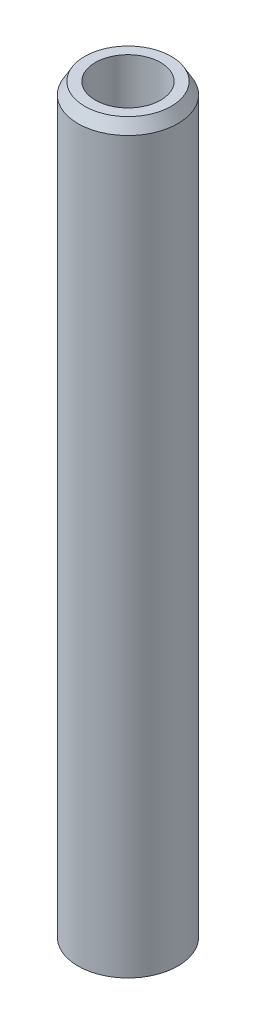
SolidWorks part; units mm, degrees
ref_plane "Front Plane" through (0, 0, 0) normal (0, 0, 1) x (1, 0, 0)
ref_plane "Top Plane" through (0, 0, 0) normal (0, 1, 0) x (1, 0, 0)
ref_plane "Right Plane" through (0, 0, 0) normal (1, 0, 0) x (0, 0, -1)
sketch "Sketch1" plane through (0, 0, 0) normal (0, 1, 0) x (1, 0, 0)
  circle A0 centre (0, 0) radius 12.5
  dimension "SHAFT_OD" = 25
extrude "Boss-Extrude1" add sketch "Sketch1" along normal blind 187.0488
sketch "Sketch2" plane through (0, 0, 0) normal (0, 1, 0) x (1, 0, 0)
  circle A0 centre (0, 0) radius 8.1687
  dimension "BORE_D" = 16.3373
extrude "Cut-Extrude1" cut sketch "Sketch2" along normal through all
chamfer "Chamfer1" distance 2.912 angle 30 2 edges at (0, 187.0488, 12.5) (0, 0, 12.5) first distance on face at (0, 187.0488, 12.5) first distance on face at (0, 0, 8.1687)
